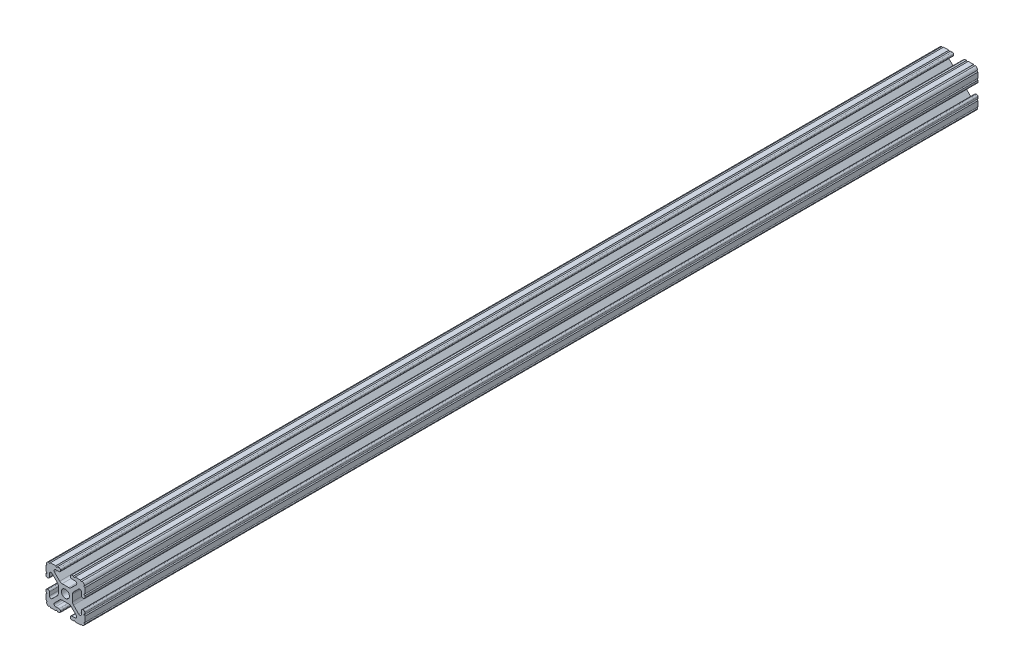
SolidWorks part; units mm, degrees
ref_plane "Front Plane" through (0, 0, 0) normal (0, 0, 1) x (1, 0, 0)
ref_plane "Top Plane" through (0, 0, 0) normal (0, 1, 0) x (1, 0, 0)
ref_plane "Right Plane" through (0, 0, 0) normal (1, 0, 0) x (0, 0, -1)
sketch "Sketch2" plane through (0, 0, 0) normal (0, 0, 1) x (1, 0, 0)
  line L0 (0, 12.7) -> (0, -12.7) construction
  line L1 (-12.7, 0) -> (12.7, 0) construction
  line L2 (3.2512, -12.7) -> (12.7, -12.7)
  line L3 (12.7, -12.7) -> (12.7, -3.2512)
  line L4 (3.2512, -12.7) -> (3.2512, -10.4902)
  line L5 (3.2512, -10.4902) -> (8.9276, -10.4902)
  line L6 (8.9276, -10.4902) -> (3.0856, -4.6482)
  line L7 (0, 0) -> (12.7, -12.7) construction
  line L8 (12.7, -3.2512) -> (10.4902, -3.2512)
  line L9 (10.4902, -3.2512) -> (10.4902, -8.9276)
  line L10 (10.4902, -8.9276) -> (4.6482, -3.0856)
  circle A0 centre (0, 0) radius 2.6035
  arc A1 (6.3485, -10.4902) -> (7.1039, -8.6665) centre (6.3485, -9.4219) ccw construction
  point P8 (0, -4.6482)
  dimension "Center Hole Diameter" = 5.207
  dimension "Rail Height" = 25.4
  dimension "Rail Width" = 25.4
  dimension "T-Slot Width" = 6.5024
  dimension "Slot Inner Width" = 14.8336
  dimension "Thickness" = 2.2098
  dimension "Slot Depth" = 5.842
  dimension "D1" = 2.2098
sketch "Sketch3" plane through (0, 0, 0) normal (1, 0, 0) x (0, 0, -1)
  line L0 (-228.6, -12.7) -> (228.6, -12.7) construction
  line L1 (-205.74, 0) -> (205.74, 0) construction
  dimension "Length" = 457.2
  dimension "D1" = 411.48
sketch "Sketch4" plane through (0, 0, 0) normal (0, 0, 1) x (1, 0, 0)
  line L0 (4.1904, -12.7) -> (10.1173, -12.7)
  line L1 (3.2512, -12.7) -> (12.7, -12.7) construction
  line L2 (3.2512, -12.7) -> (3.2512, -10.4902) construction
  line L3 (3.2512, -10.4902) -> (8.9276, -10.4902) construction
  line L4 (3.2512, -11.4294) -> (3.2512, -11.7608)
  line L5 (4.1904, -10.4902) -> (6.3485, -10.4902)
  line L6 (0, -4.6482) -> (2.164, -4.6482)
  line L7 (8.9276, -10.4902) -> (3.0856, -4.6482) construction
  line L8 (3.7373, -5.2999) -> (7.1039, -8.6665)
  line L9 (12.7, -12.7) -> (12.7, -3.2512) construction
  line L10 (10.4902, -8.9276) -> (4.6482, -3.0856) construction
  line L11 (10.4902, -3.2512) -> (10.4902, -8.9276) construction
  line L12 (10.4902, -6.3485) -> (10.4902, -4.1904)
  line L13 (12.7, -3.2512) -> (10.4902, -3.2512) construction
  line L14 (11.4294, -3.2512) -> (11.7608, -3.2512)
  line L15 (12.7, -4.1904) -> (12.7, -10.1173)
  line L16 (8.6665, -7.1039) -> (5.2999, -3.7373)
  line L17 (4.6482, 0) -> (4.6482, -2.164)
  line L18 (-12.7, 0) -> (12.7, 0) construction
  line L19 (0, -4.6482) -> (0, -2.6035)
  line L20 (0, 12.7) -> (0, -12.7) construction
  line L21 (4.6482, 0) -> (2.6035, 0)
  arc A0 (3.2512, -11.7608) -> (4.1904, -12.7) centre (4.1904, -11.7608) ccw
  arc A2 (3.2512, -11.4294) -> (4.1904, -10.4902) centre (4.1904, -11.4294) cw
  arc A3 (6.3485, -10.4902) -> (7.1039, -8.6665) centre (6.3485, -9.4219) ccw
  arc A4 (2.164, -4.6482) -> (3.7373, -5.2999) centre (2.164, -6.8732) cw
  arc A5 (10.1173, -12.7) -> (12.7, -10.1173) centre (10.1173, -10.1173) ccw
  arc A6 (8.6665, -7.1039) -> (10.4902, -6.3485) centre (9.4219, -6.3485) ccw
  arc A7 (10.4902, -4.1904) -> (11.4294, -3.2512) centre (11.4294, -4.1904) cw
  arc A8 (11.7608, -3.2512) -> (12.7, -4.1904) centre (11.7608, -4.1904) cw
  arc A9 (5.2999, -3.7373) -> (4.6482, -2.164) centre (6.8732, -2.164) cw
  circle A10 centre (0, 0) radius 2.6035 construction
  arc A11 (0, -2.6035) -> (2.6035, 0) centre (0, 0) ccw
  dimension "D1" = 2.5827
  dimension "D2" = 2.225
  dimension "D3" = 0.9392
extrude "Boss-Extrude1" add sketch "Sketch4" along normal mid plane 584
sketch "Sketch5" plane through (0, 0, 0) normal (0, 0, 1) x (1, 0, 0)
  line L0 (3.2512, -12.7) -> (12.7, -12.7) construction
  line L1 (4.1904, -10.4902) -> (6.3485, -10.4902) construction
  line L3 (0, 0) -> (12.7, -12.7) construction
  line L4 (6.3485, -10.4902) -> (6.3485, -12.7) construction
  line L5 (8.9276, -10.4902) -> (3.0856, -4.6482) construction
  circle A0 centre (10.3562, -12.7) radius 0.5524
  circle A1 centre (5.796, -12.7) radius 0.5524
  circle A2 centre (12.7, -10.3562) radius 0.5524
  circle A3 centre (12.7, -5.796) radius 0.5524
  point P10 (5.2694, -10.4902)
  point P12 (9.4219, -6.3485)
  dimension "D1" = 1.1049
extrude "Cut-Extrude1" cut sketch "Sketch5" against normal through all both and the other way through all
mirror "Mirror1" about plane through (0, 0, 0) normal (1, 0, 0) of bodies 137 134
mirror "Mirror2" about plane through (0, 0, 0) normal (0, 1, 0) of bodies 135
equation "\"D1@Boss-Extrude1\"=\"Length@Sketch3\""
equation "\"D1@Sketch2\"=\"Thickness@Sketch2\""
equation "\"D2@Sketch4\"=\"Slot Inner Width@Sketch2\"*0.15"
equation "\"D1@Sketch4\"=\"D3@Sketch4\"*2.75"
equation "\"D3@Sketch4\"=\"Thickness@Sketch2\"*0.425"
equation "\"D1@Sketch5\"=\"Thickness@Sketch2\"*0.5"
equation "\"D1@Sketch3\"=\"Length@Sketch3\"*0.9"
